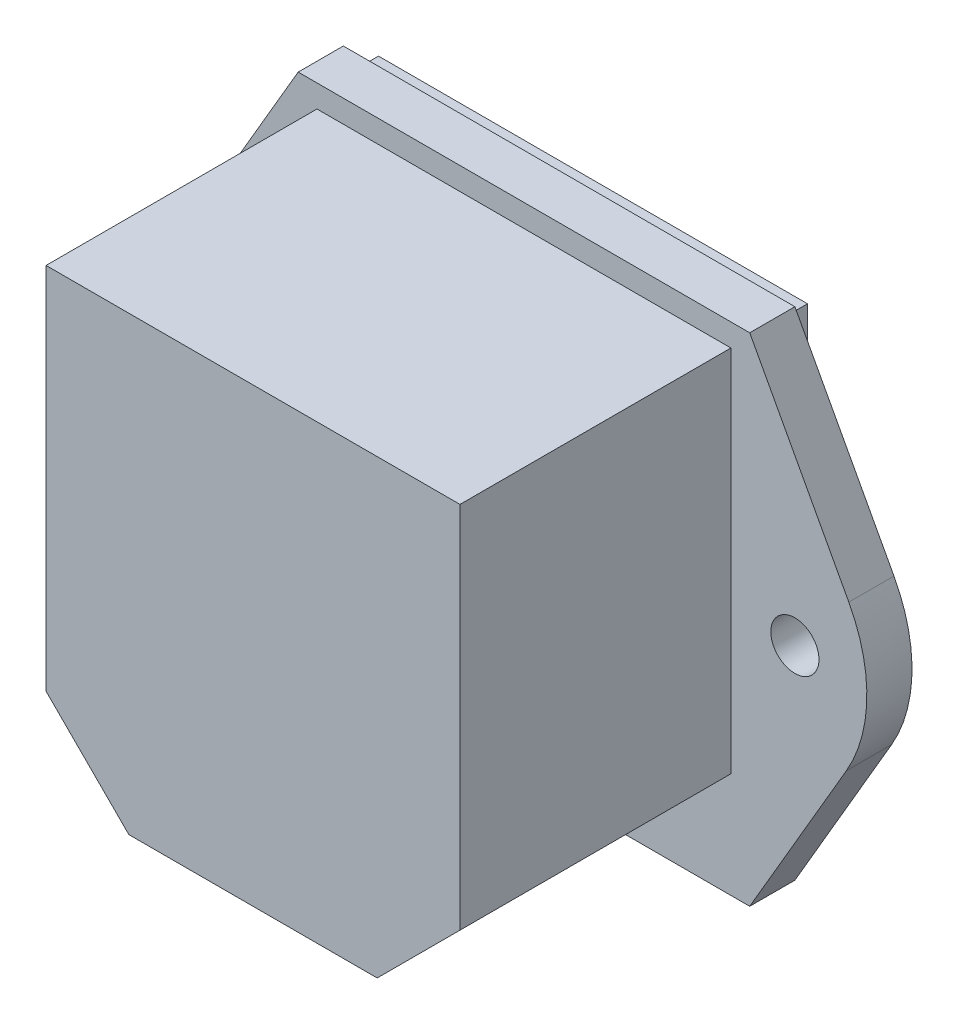
SolidWorks part; units mm, degrees
ref_plane "Plan de face" through (0, 0, 0) normal (0, 0, 1) x (1, 0, 0)
ref_plane "Plan de dessus" through (0, 0, 0) normal (0, 1, 0) x (1, 0, 0)
ref_plane "Plan de droite" through (0, 0, 0) normal (1, 0, 0) x (0, 0, -1)
sketch "Esquisse1" plane through (0, 0, 0) normal (0, 0, 1) x (1, 0, 0)
  line L1 (-17.5694, 7.1212) -> (12.4306, 7.1212)
  line L2 (-17.5694, 7.1212) -> (-17.5694, -25.8788)
  line L3 (-17.5694, -25.8788) -> (12.4306, -25.8788)
  line L4 (12.4306, 7.1212) -> (12.4306, -25.8788)
  dimension "D1" = 30
  dimension "D2" = 33
extrude "Boss.-Extru.1" add sketch "Esquisse1" along normal blind 3
sketch "Esquisse2" plane through (0, 0, 3) normal (0, 0, 1) x (1, 0, 0)
  line L0 (-16.3194, -4.8788) -> (11.1806, -4.8788)
  line L1 (11.1806, -4.8788) -> (11.1806, -18.8788)
  line L2 (11.1806, -18.8788) -> (5.6806, -24.3788)
  line L3 (5.6806, -24.3788) -> (-10.8194, -24.3788)
  line L4 (-10.8194, -24.3788) -> (-16.3194, -18.8788)
  line L5 (-16.3194, -18.8788) -> (-16.3194, -4.8788)
  line L7 (-17.5694, -25.8788) -> (12.4306, -25.8788) construction
  line L8 (-17.5694, 7.1212) -> (-17.5694, -25.8788) construction
  dimension "D1" = 27.5
  dimension "D2" = 19.5
  dimension "D3" = 1.5
  dimension "D4" = 1.25
  dimension "D5" = 135
  dimension "D6" = 135
  dimension "D7" = 14
  dimension "D8" = 14
extrude "Boss.-Extru.2" add sketch "Esquisse2" along normal blind 18
shell "Coque1" thickness 3 removed face at (-2.5694, -9.3788, 0)
sketch "Esquisse3" plane through (0, 0, 18) normal (0, 0, -1) x (-1, 0, 0)
  line L0 (-8.1806, -17.6361) -> (-8.1806, -7.8788) construction
  line L1 (1.8194, -14.6288) -> (3.3194, -14.6288)
  line L2 (1.8194, -14.6288) -> (1.8194, -17.6288)
  line L3 (1.8194, -17.6288) -> (3.3194, -17.6288)
  line L4 (3.3194, -14.6288) -> (3.3194, -17.6288)
  line L5 (-4.1806, -11.6288) -> (-2.6806, -11.6288)
  line L6 (-4.1806, -11.6288) -> (-4.1806, -14.6288)
  line L7 (-4.1806, -14.6288) -> (-2.6806, -14.6288)
  line L8 (-2.6806, -11.6288) -> (-2.6806, -14.6288)
  line L9 (7.8194, -11.6288) -> (9.3194, -11.6288)
  line L10 (7.8194, -11.6288) -> (7.8194, -14.6288)
  line L11 (7.8194, -14.6288) -> (9.3194, -14.6288)
  line L12 (9.3194, -11.6288) -> (9.3194, -14.6288)
  line L14 (-8.1806, -7.8788) -> (13.3194, -7.8788) construction
  line L15 (9.5768, -21.3788) -> (-4.4379, -21.3788) construction
  line L16 (13.3194, -7.8788) -> (13.3194, -17.6361) construction
  dimension "D1" = 1.5
  dimension "D2" = 3
  dimension "D3" = 1.5
  dimension "D4" = 3
  dimension "D5" = 1.5
  dimension "D6" = 3
  dimension "D7" = 10
  dimension "D8" = 6.75
  dimension "D9" = 6.75
  dimension "D10" = 6.75
  dimension "D11" = 4
  dimension "D12" = 4
extrude "Boss.-Extru.3" add sketch "Esquisse3" along normal blind 15
fillet "Congé1" radius 0.5 12 edges at (-8.5694, -11.6288, 3) (-9.3194, -13.1288, 3) (-8.5694, -14.6288, 3) (-7.8194, -13.1288, 3) (-2.5694, -14.6288, 3) (-3.3194, -16.1288, 3) (-2.5694, -17.6288, 3) (-1.8194, -16.1288, 3) (3.4306, -14.6288, 3) (4.1806, -13.1288, 3) (3.4306, -11.6288, 3) (2.6806, -13.1288, 3)
sketch "Esquisse4" plane through (0, -4.8788, 0) normal (0, 1, 0) x (1, 0, 0)
  line L4 (11.1806, -3) -> (-16.3194, -3)
  line L5 (-16.3194, -3) -> (-16.3194, -21)
  line L6 (-16.3194, -21) -> (11.1806, -21)
  line L7 (11.1806, -21) -> (11.1806, -3)
  line L8 (11.1806, -3) -> (-16.3194, -3)
  line L9 (-16.3194, -3) -> (-16.3194, -21)
  line L10 (-16.3194, -21) -> (11.1806, -21)
  line L11 (11.1806, -21) -> (11.1806, -3)
  dimension "D1" = 0
extrude "Boss.-Extru.4" add sketch "Esquisse4" along normal offset from surface (10.5 mm away) 1.5 up to face at (-2.5694, 7.1212, 1.5)
sketch "Esquisse6" plane through (0, 0, 0) normal (0, 0, -1) x (-1, 0, 0)
  line L0 (20.5694, -9.3788) -> (-15.4306, -9.3788) construction
  line L1 (17.5694, -25.8788) -> (-12.4306, -25.8788) construction
  line L2 (17.5694, -25.8788) -> (27.5694, -10.0241)
  line L3 (27.5694, -10.0241) -> (17.5694, 7.1212)
  line L4 (17.5694, 7.1212) -> (17.5694, -25.8788)
  line L5 (-12.4306, 7.1212) -> (-12.4306, -25.8788)
  line L6 (-12.4306, -25.8788) -> (-21.6779, -10.0241)
  line L7 (-21.6779, -10.0241) -> (-12.4306, 7.1212)
  circle A0 centre (20.5694, -9.3788) radius 1.6
  circle A1 centre (-15.4306, -9.3788) radius 1.6
  point P4 (2.5694, -9.3788)
  point P7 (2.5694, -25.8788)
  point P17 (0, 0)
  point P19 (17.5694, -9.3788)
  dimension "D1" = 3.2
  dimension "D2" = 36
  dimension "D3" = 10
extrude "Boss.-Extru.5" add sketch "Esquisse6" against normal up to surface (3 mm away) up to face at (-2.5694, -9.3788, 3)
fillet "Congé2" radius 10 2 edges at (21.6779, -10.0241, 1.5) (-27.5694, -10.0241, 1.5)
sketch "Esquisse7" plane through (0, 0, 0) normal (0, 0, -1) x (-1, 0, 0)
  line L0 (-4.4379, -21.3788) -> (-8.1806, -17.6361) construction
  line L1 (-8.1806, -17.6361) -> (-8.1806, -7.8788) construction
  line L2 (-8.1806, -7.8788) -> (13.3194, -7.8788) construction
  line L3 (13.3194, -7.8788) -> (13.3194, -17.6361) construction
  line L4 (13.3194, -17.6361) -> (9.5768, -21.3788) construction
  line L5 (9.5768, -21.3788) -> (-4.4379, -21.3788) construction
  line L6 (-4.4379, -21.3788) -> (-8.1806, -17.6361)
  line L7 (-8.1806, -17.6361) -> (-8.1806, -7.8788)
  line L8 (-8.1806, -7.8788) -> (13.3194, -7.8788)
  line L9 (13.3194, -7.8788) -> (13.3194, -17.6361)
  line L10 (13.3194, -17.6361) -> (9.5768, -21.3788)
  line L11 (9.5768, -21.3788) -> (-4.4379, -21.3788)
  line L12 (17.5694, -25.8788) -> (-12.4306, -25.8788) construction
  line L13 (16.8194, -24.8788) -> (-11.6806, -24.8788)
  line L14 (16.8194, -24.8788) -> (16.8194, 6.1212)
  line L15 (16.8194, 6.1212) -> (-11.6806, 6.1212)
  line L16 (-11.6806, -24.8788) -> (-11.6806, 6.1212)
  arc A0 (24.3326, -15.1559) -> (24.5126, -4.783) centre (15.8745, -9.8212) ccw construction
  circle A3 centre (20.5694, -9.3788) radius 1.6 construction
  circle A4 centre (20.5694, -9.3788) radius 1.6 construction
  point P14 (25.873, -9.9946)
  point P15 (2.5694, -24.8788)
  point P18 (2.5694, -25.8788)
  point P21 (0, 0)
  point P22 (16.8194, -9.3788)
  dimension "D1" = 31
  dimension "D2" = 28.5
extrude "Boss.-Extru.6" add sketch "Esquisse7" along normal blind 1.5875
